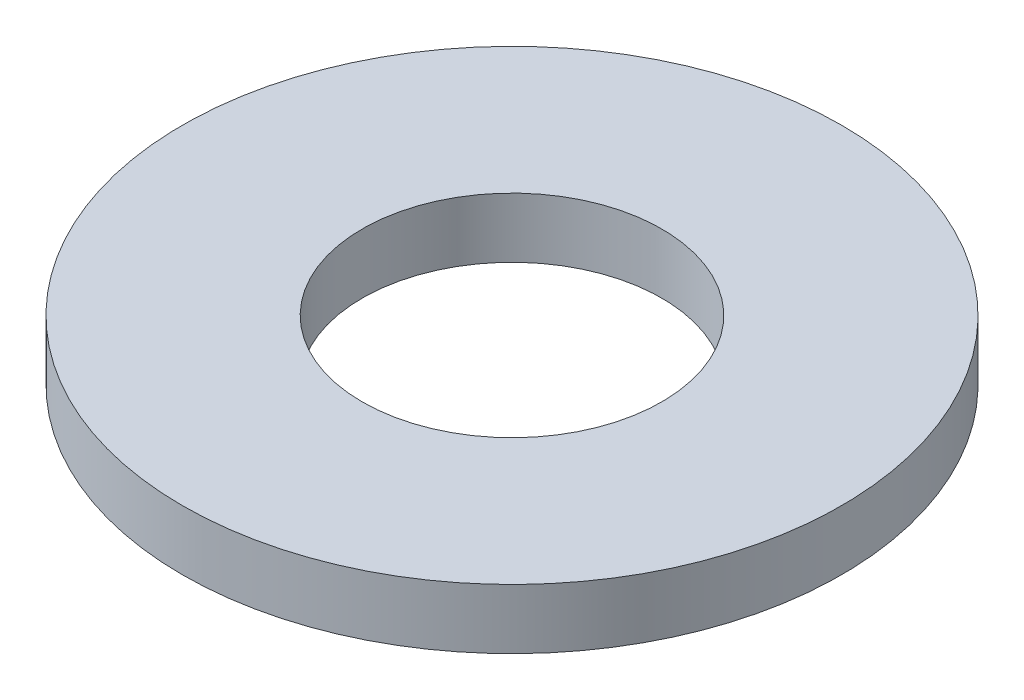
SolidWorks part; units mm, degrees
ref_plane "Front Plane" through (0, 0, 0) normal (0, 0, 1) x (1, 0, 0)
ref_plane "Top Plane" through (0, 0, 0) normal (0, 1, 0) x (1, 0, 0)
ref_plane "Right Plane" through (0, 0, 0) normal (1, 0, 0) x (0, 0, -1)
sketch "Sketch1" plane through (0, 0, 0) normal (0, 1, 0) x (1, 0, 0)
  circle A0 centre (0, 0) radius 5
  circle A1 centre (0, 0) radius 11
  dimension "D1" = 10
  dimension "D2" = 22
extrude "Boss-Extrude1" add sketch "Sketch1" along normal blind 2
